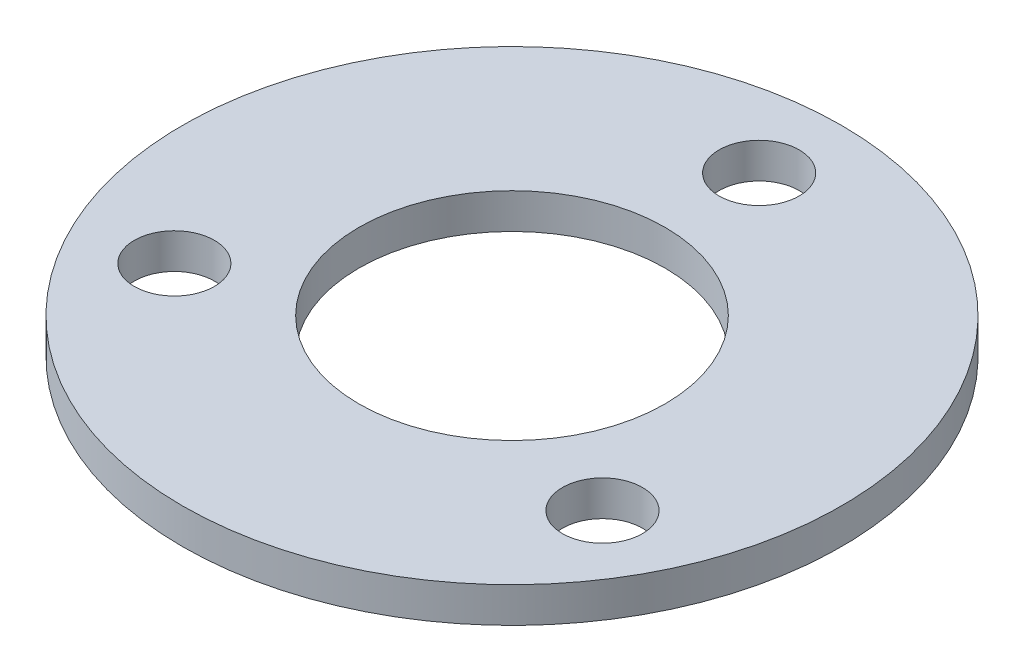
SolidWorks part; units mm, degrees
ref_plane "Front Plane" through (0, 0, 0) normal (0, 0, 1) x (1, 0, 0)
ref_plane "Top Plane" through (0, 0, 0) normal (0, 1, 0) x (1, 0, 0)
ref_plane "Right Plane" through (0, 0, 0) normal (1, 0, 0) x (0, 0, -1)
sketch "Sketch1" plane through (0, 0, 0) normal (0, 1, 0) x (1, 0, 0)
  circle A0 centre (0, 0) radius 14
  circle A1 centre (0, 0) radius 6.5
  circle A2 centre (0, 0) radius 10.5 construction
  circle A3 centre (0, 10.5) radius 1.7
  circle A4 centre (9.0933, -5.25) radius 1.7
  circle A5 centre (-9.0933, -5.25) radius 1.7
  point P13 (0, 0)
  dimension "D1" = 28
  dimension "D2" = 13
  dimension "D3" = 21
  dimension "D4" = 3.4
  dimension "D5" = 3
extrude "Boss-Extrude1" add sketch "Sketch1" along normal blind 1.5
